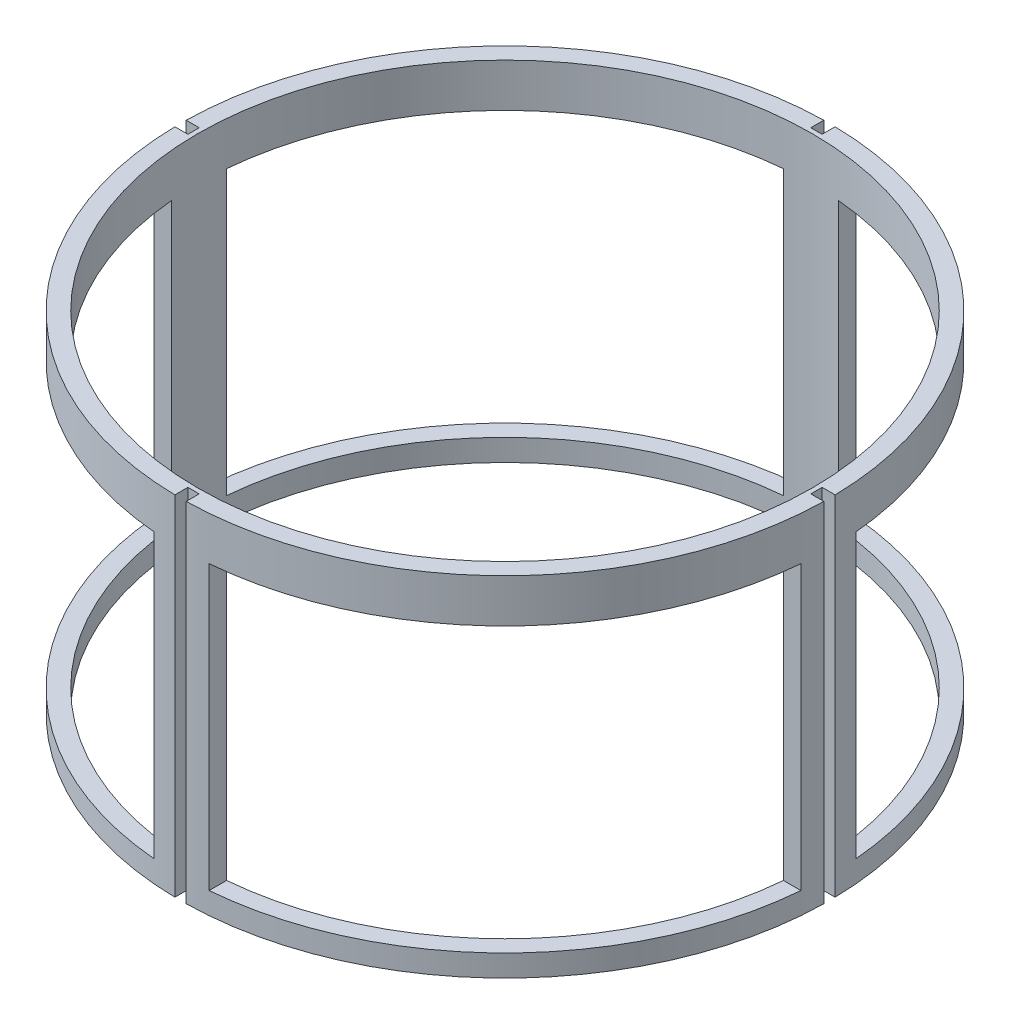
SolidWorks part; units mm, degrees
ref_plane "Front" through (0, 0, 0) normal (0, 0, 1) x (1, 0, 0)
ref_plane "Top" through (0, 0, 0) normal (0, 1, 0) x (1, 0, 0)
ref_plane "Right" through (0, 0, 0) normal (1, 0, 0) x (0, 0, -1)
sketch "Sketch1" plane through (0, 0, 0) normal (0, 1, 0) x (1, 0, 0)
  circle A0 centre (0, 0) radius 89.535
  circle A1 centre (0, 0) radius 94.615
  dimension "Inner Diameter" = 179.07
  dimension "Outer Diameter" = 189.23
extrude "Boss-Extrude1" add sketch "Sketch1" against normal blind 101.6
sketch "Sketch5" plane through (0, 0, 0) normal (0, 1, 0) x (1, 0, 0)
  line L0 (0, 114.2751) -> (0, -136.7211) construction
  line L1 (-124.857, 0) -> (116.4345, 0) construction
  line L2 (-1.651, 90.805) -> (1.651, 90.805)
  line L3 (1.651, 90.805) -> (1.651, 95.885)
  line L4 (1.651, 95.885) -> (-1.651, 95.885)
  line L5 (-1.651, 95.885) -> (-1.651, 90.805)
  line L6 (1.651, -95.885) -> (-1.651, -95.885)
  line L7 (1.651, -90.805) -> (1.651, -95.885)
  line L8 (-1.651, -90.805) -> (1.651, -90.805)
  line L9 (-1.651, -95.885) -> (-1.651, -90.805)
  line L10 (-90.805, 1.651) -> (-90.805, -1.651)
  line L11 (-90.805, -1.651) -> (-95.885, -1.651)
  line L12 (-95.885, -1.651) -> (-95.885, 1.651)
  line L13 (-95.885, 1.651) -> (-90.805, 1.651)
  line L14 (95.885, -1.651) -> (95.885, 1.651)
  line L15 (90.805, -1.651) -> (95.885, -1.651)
  line L16 (90.805, 1.651) -> (90.805, -1.651)
  line L17 (95.885, 1.651) -> (90.805, 1.651)
  dimension "D1" = 1.651
  dimension "D2" = 1.651
  dimension "D3" = 5.08
  dimension "D4" = 90.805
  dimension "D5" = 1.651
  dimension "D6" = 90.805
extrude "Cut-Extrude1" cut sketch "Sketch5" against normal blind 101.6
sketch "Sketch7" plane through (0, 0, 0) normal (0, 1, 0) x (1, 0, 0)
  line L0 (89.1768, -8.001) -> (94.2761, -8.001)
  line L1 (8.001, -89.1768) -> (8.001, -94.2761)
  line L2 (1.651, -94.6006) -> (1.651, -90.805) construction
  line L3 (90.805, -1.651) -> (94.6006, -1.651) construction
  arc A0 (89.1768, -8.001) -> (8.001, -89.1768) centre (0, 0) cw
  circle A1 centre (0, 0) radius 89.535 construction
  arc A2 (94.2761, -8.001) -> (8.001, -94.2761) centre (0, 0) cw
  arc A3 (1.651, -94.6006) -> (94.6006, -1.651) centre (0, 0) ccw construction
  point P15 (92.7028, -1.651)
  dimension "D3" = 94.615
  dimension "D4" = 89.535
  dimension "D1" = 6.35
  dimension "D2" = 6.35
extrude "Cut-Extrude2" cut sketch "Sketch7" against normal blind 82.55 from offset 12.7 offset against normal yes
pattern_circular "CirPattern1" count 4 over 360 about axis through (0, 0, 0) along (0, 1, 0) of "Cut-Extrude2"
equation "\"D4@Sketch5\"=(\"Inner Diameter\"/2)+((\"Outer Diameter\"-\"Inner Diameter\")/8)"
equation "\"D6@Sketch5\"=(\"Inner Diameter\"/2)+((\"Outer Diameter\"-\"Inner Diameter\")/8)"
equation "\"D1@Cut-Extrude1\"=\"Fin Length\""
equation "\"D3@Sketch7\"=\"Outer Diameter\"/2"
equation "\"D4@Sketch7\"=\"Inner Diameter\"/2"
